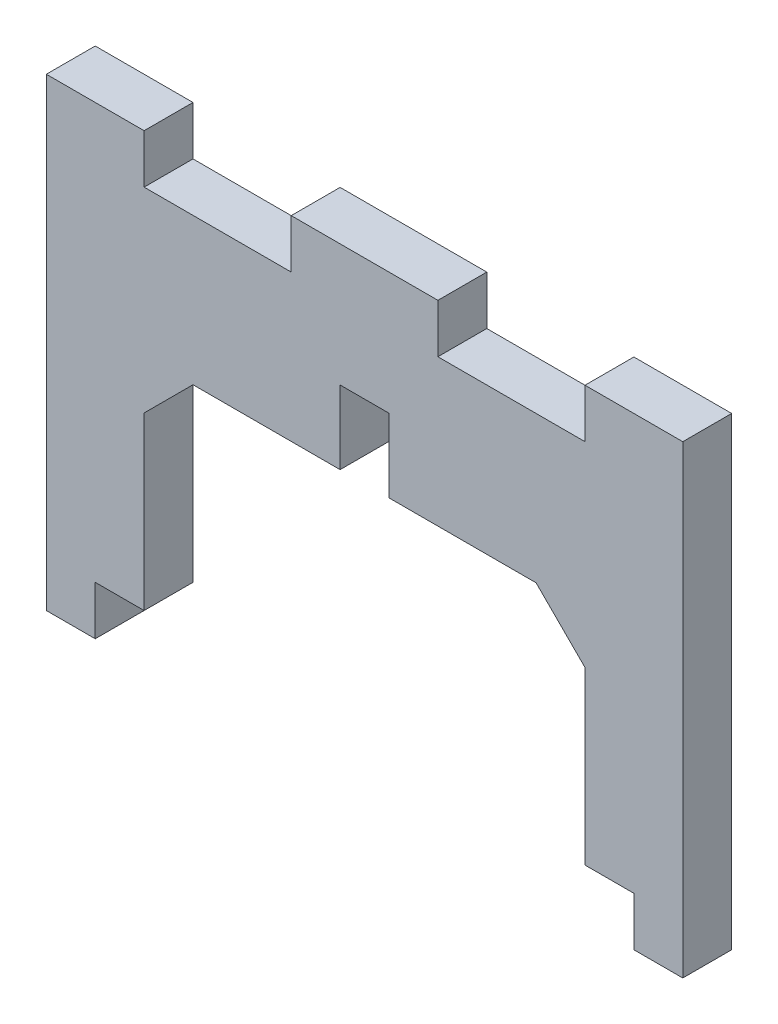
SolidWorks part; units mm, degrees
ref_plane "Front Plane" through (0, 0, 0) normal (0, 0, 1) x (1, 0, 0)
ref_plane "Top Plane" through (0, 0, 0) normal (0, 1, 0) x (1, 0, 0)
ref_plane "Right Plane" through (0, 0, 0) normal (1, 0, 0) x (0, 0, -1)
sketch "Sketch1" plane through (0, 0, 0) normal (0, 0, 1) x (1, 0, 0)
  line L0 (0, 0) -> (4, 0)
  line L1 (4, 0) -> (4, 4)
  line L2 (4, 4) -> (8, 4)
  line L3 (8, 4) -> (8, 22)
  line L4 (8, 22) -> (24.035, 22)
  line L5 (24.035, 22) -> (24.035, 28)
  line L6 (24.035, 28) -> (28.035, 28)
  line L7 (26.035, 28) -> (26.035, 34)
  line L8 (52.07, 34) -> (0, 34)
  line L9 (0, 34) -> (0, 0)
  line L10 (52.07, 34) -> (52.07, 0)
  line L11 (28.035, 22) -> (28.035, 28)
  line L12 (44.07, 22) -> (28.035, 22)
  line L13 (44.07, 4) -> (44.07, 22)
  line L14 (48.07, 4) -> (44.07, 4)
  line L15 (48.07, 0) -> (48.07, 4)
  line L16 (52.07, 0) -> (48.07, 0)
  dimension "D1" = 4
  dimension "D2" = 8
  dimension "D3" = 4
  dimension "D4" = 12
  dimension "D5" = 2
  dimension "D6" = 26.035
  dimension "D7" = 30
  dimension "D8" = 6
extrude "Boss-Extrude1" add sketch "Sketch1" along normal blind 4 contours L8 L9 L0 L1 L2 L3 L4 L5 L6 L7 | L16 L10 L8 L7 L6 L11 L12 L13 L14 L15 region at (9.5011, 22.4833, 0) region at (42.5689, 22.4833, 0)
chamfer "Chamfer1" distance 4 angle 45 2 edges at (44.07, 22, 2) (8, 22, 2)
sketch "Sketch2" plane through (0, 0, 4) normal (0, 0, 1) x (1, 0, 0)
  line L0 (0, 34) -> (0, 38)
  line L1 (0, 38) -> (8, 38)
  line L2 (8, 38) -> (8, 34)
  line L3 (52.07, 34) -> (0, 34) construction
  line L4 (8, 34) -> (0, 34)
  line L6 (52.07, 34) -> (44.07, 34)
  line L7 (52.07, 34) -> (52.07, 38)
  line L8 (52.07, 38) -> (44.07, 38)
  line L9 (44.07, 34) -> (44.07, 38)
  line L10 (32.035, 34) -> (20.035, 34)
  line L11 (32.035, 34) -> (32.035, 38)
  line L12 (32.035, 38) -> (20.035, 38)
  line L13 (20.035, 34) -> (20.035, 38)
  line L19 (24.035, 28) -> (28.035, 28) construction
  point P18 (0, 0)
  point P20 (26.035, 28)
  point P21 (26.035, 38)
  dimension "D1" = 8
  dimension "D2" = 4
  dimension "D3" = 12
extrude "Boss-Extrude2" add sketch "Sketch2" against normal up to surface (4 mm away) up to face at (26.035, 14.6667, 0)
